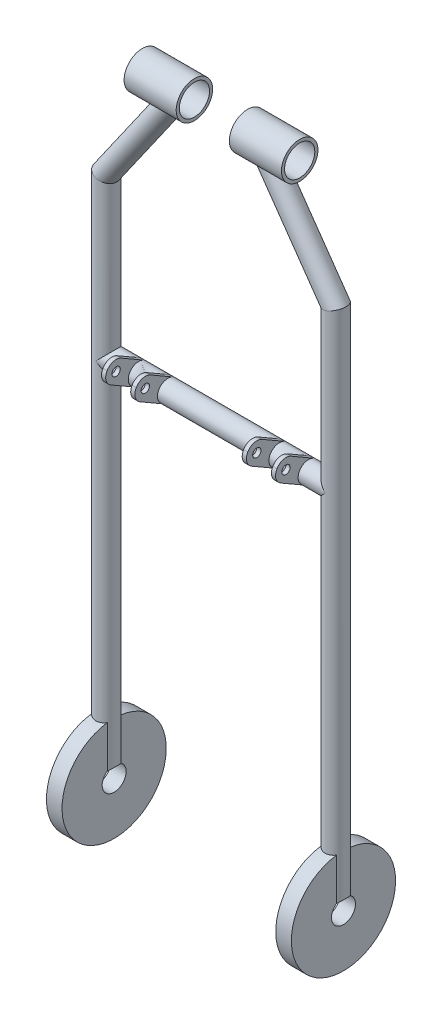
SolidWorks part; units mm, degrees
ref_plane "Alzado" through (0, 0, 0) normal (0, 0, 1) x (1, 0, 0)
ref_plane "Planta" through (0, 0, 0) normal (0, 1, 0) x (1, 0, 0)
ref_plane "Vista lateral" through (0, 0, 0) normal (1, 0, 0) x (0, 0, -1)
sketch "Croquis1" plane through (0, 0, 0) normal (1, 0, 0) x (0, 0, -1)
  circle A0 centre (0, 0) radius 17.5
  circle A1 centre (0, 0) radius 14.5
  dimension "D1" = 35
  dimension "D2" = 3
extrude "Saliente-Extruir1" add sketch "Croquis1" along normal blind 50
sketch "Croquis2" plane through (0, 0, 0) normal (0, 0, 1) x (1, 0, 0)
  line L0 (25, -17.5) -> (-34.5176, -102.5)
  line L1 (-34.5176, -102.5) -> (-34.5176, -602.5)
  line L2 (-34.5176, -102.5) -> (29.5486, -102.5) construction
  line L3 (25, 17.5) -> (25, -17.5) construction
  line L4 (50, 17.5) -> (0, 17.5) construction
  line L5 (0, -17.5) -> (50, -17.5) construction
  line L6 (0, 0) -> (50, 0) construction
  line L7 (50, -17.5) -> (50, 17.5) construction
  dimension "D1" = 85
  dimension "D2" = 500
  dimension "D3" = 55
  dimension "D4" = 64.0663
ref_plane "Plano1" through (25, -17.5, 0) normal (-0.5736, -0.8192, 0) x (0, 0, 1)
sketch "Croquis3" plane through (25, -17.5, 0) normal (-0.5736, -0.8192, 0) x (0, 0, 1)
  circle A0 centre (0, 0) radius 10
  circle A1 centre (0, 0) radius 7
  dimension "D2" = 3
  dimension "D1" = 20
sweep "Barrer1" add profiles "Croquis3" path "Croquis2"
sketch "Croquis4" plane through (50, 0, 0) normal (1, 0, 0) x (0, 0, -1)
  circle A0 centre (0, 0) radius 14.5 construction
  circle A1 centre (0, 0) radius 14.5
extrude "Cortar-Extruir1" cut sketch "Croquis4" against normal through all
sketch "Croquis5" plane through (0.0024, 0.0035, 0) normal (0.5736, 0.8192, 0) x (0.8192, -0.5736, 0)
  arc A4 (40.5164, 0) -> (26.1673, 9.0048) centre (30.5164, 0) ccw
  arc A5 (37.5164, 0) -> (28.2476, 6.6221) centre (30.5164, 0) ccw
  arc A6 (28.2476, -6.6221) -> (37.5164, 0) centre (30.5164, 0) ccw
  arc A7 (26.1673, -9.0048) -> (40.5164, 0) centre (30.5164, 0) ccw
  arc A8 (40.5164, 0) -> (26.1673, 9.0048) centre (30.5164, 0) ccw
  arc A9 (37.5164, 0) -> (28.2476, 6.6221) centre (30.5164, 0) ccw
  arc A10 (28.2476, -6.6221) -> (37.5164, 0) centre (30.5164, 0) ccw
  arc A11 (26.1673, -9.0048) -> (40.5164, 0) centre (30.5164, 0) ccw
  ellipse E2 centre (0.0061, 0) end of major axis (-30.5042, 0) minor radius 17.5 (28.2476, 6.6221) -> (26.1673, 9.0048) ccw
  ellipse E3 centre (0.0061, 0) end of major axis (-30.5042, 0) minor radius 17.5 (26.1673, -9.0048) -> (28.2476, -6.6221) ccw
  ellipse E4 centre (0.0061, 0) end of major axis (-30.5042, 0) minor radius 17.5 (28.2476, 6.6221) -> (26.1673, 9.0048) ccw
  ellipse E5 centre (0.0061, 0) end of major axis (-30.5042, 0) minor radius 17.5 (26.1673, -9.0048) -> (28.2476, -6.6221) ccw
  dimension "D1" = 0
extrude "Saliente-Extruir2" add sketch "Croquis5" along normal up to body separate body
ref_plane "Plano3" through (101, 0, 0) normal (1, 0, 0) x (0, 0, -1)
sketch "Croquis6" plane through (101, 0, 0) normal (1, 0, 0) x (0, 0, -1)
  circle A0 centre (0, 0) radius 14.5 construction
  circle A1 centre (0, 0) radius 17.5 construction
  circle A2 centre (0, 0) radius 14.5
  circle A3 centre (0, 0) radius 17.5
extrude "Saliente-Extruir3" add sketch "Croquis6" along normal blind 50 separate body
sketch "Croquis7" plane through (0, 0, 0) normal (0, 0, 1) x (1, 0, 0)
  line L0 (151, -17.5) -> (151, 17.5) construction
  line L1 (101, -17.5) -> (151, -17.5) construction
  line L2 (101, 17.5) -> (101, -17.5) construction
  line L3 (151, 17.5) -> (101, 17.5) construction
  line L4 (151, -17.5) -> (151, 17.5) construction
  line L5 (101, -17.5) -> (151, -17.5) construction
  line L6 (101, 17.5) -> (101, -17.5) construction
  line L7 (151, 17.5) -> (101, 17.5) construction
  line L8 (126, -17.5) -> (185.5176, -102.5)
  line L9 (185.5176, -102.5) -> (185.5176, -602.5)
  line L10 (185.5176, -102.5) -> (99.3833, -102.5) construction
  dimension "D1" = 85
  dimension "D2" = 500
  dimension "D3" = 86.1343
  dimension "D4" = 55
ref_plane "Plano4" through (126, -17.5, 0) normal (0.5736, -0.8192, 0) x (-0.8192, -0.5736, 0)
sketch "Croquis8" plane through (126, -17.5, 0) normal (0.5736, -0.8192, 0) x (-0.8192, -0.5736, 0)
  circle A0 centre (0, 0) radius 10
  circle A1 centre (0, 0) radius 7
  dimension "D2" = 3
  dimension "D1" = 20
sweep "Barrer2" add profiles "Croquis8" path "Croquis7"
sketch "Croquis9" plane through (49.675, -70.9433, 0) normal (-0.5736, 0.8192, 0) x (0.8192, 0.5736, 0)
  arc A2 (95.4443, 6.6221) -> (95.4443, -6.6221) centre (93.1756, 0) ccw
  arc A3 (97.5246, 9.0048) -> (97.5246, -9.0048) centre (93.1756, 0) ccw
  arc A4 (95.4443, 6.6221) -> (95.4443, -6.6221) centre (93.1756, 0) ccw
  arc A5 (97.5246, 9.0048) -> (97.5246, -9.0048) centre (93.1756, 0) ccw
  ellipse E2 centre (123.6859, 0) end of major axis (93.1756, 0) minor radius 17.5 (97.5246, 9.0048) -> (95.4443, 6.6221) ccw
  ellipse E3 centre (123.6859, 0) end of major axis (93.1756, 0) minor radius 17.5 (95.4443, -6.6221) -> (97.5246, -9.0048) ccw
  ellipse E4 centre (123.6859, 0) end of major axis (93.1756, 0) minor radius 17.5 (97.5246, 9.0048) -> (95.4443, 6.6221) ccw
  ellipse E5 centre (123.6859, 0) end of major axis (93.1756, 0) minor radius 17.5 (95.4443, -6.6221) -> (97.5246, -9.0048) ccw
  dimension "D1" = 0
extrude "Saliente-Extruir4" add sketch "Croquis9" along normal up to surface up to face at (132.5056, -16.5721, 0.0091)
sketch "Croquis10" plane through (0, 0, 0) normal (1, 0, 0) x (0, 0, -1)
  line L0 (10, -102.5) -> (10, -14.3614) construction
  line L1 (-10, -14.3614) -> (-10, -102.5) construction
  line L2 (10, -602.5) -> (10, -102.5) construction
  line L3 (-10, -102.5) -> (-10, -602.5) construction
  line L4 (10, -102.5) -> (10, -14.3614) construction
  line L5 (-10, -14.3614) -> (-10, -102.5) construction
  line L6 (10, -602.5) -> (10, -102.5) construction
  line L7 (-10, -102.5) -> (-10, -602.5) construction
  line L10 (0, -602.5) -> (0, -11.7642) construction
  circle A0 centre (0, -254.3614) radius 10
  dimension "D2" = 20
  dimension "D1" = 240
extrude "Saliente-Extruir5" add sketch "Croquis10" along normal up to surface and the other way up to surface contours A0 up to face at (195.5176, -99.347, 0) other way up to face at (-44.5176, -99.347, 0)
sketch "Croquis11" plane through (0, -602.5, 0) normal (0, -1, 0) x (1, 0, 0)
  line L0 (-34.5176, 0) -> (-44.5176, 0)
  circle A0 centre (-34.5176, 0) radius 10 construction
  circle A1 centre (-34.5176, 0) radius 10 construction
ref_plane "Plano5" through (-34.5176, -602.5, 0) normal (-1, 0, 0) x (0, 0, 1)
sketch "Croquis12" plane through (-34.5176, -602.5, 0) normal (-1, 0, 0) x (0, 0, 1)
  line L0 (-10, 0) -> (10, 0) construction
  circle A0 centre (0, 0) radius 50
  dimension "D1" = 100
extrude "Saliente-Extruir6" add sketch "Croquis12" along normal mid plane 15
chamfer "Chaflán3" distance 7 angle 45 2 edges at (-25.1635, -602.5, -3.5355) (-25.1635, -602.5, 3.5355)
chamfer "Chaflán4" distance 7 angle 45 1 edges at (-44.5176, -602.5, 0)
sketch "Croquis13" plane through (0, -602.5, 0) normal (0, -1, 0) x (1, 0, 0)
  line L0 (185.5176, 0) -> (175.5176, 0) construction
  circle A0 centre (185.5176, 0) radius 10 construction
  circle A1 centre (185.5176, 0) radius 10 construction
ref_plane "Plano6" through (185.5176, -602.5, 0) normal (-1, 0, 0) x (0, 0, 1)
sketch "Croquis14" plane through (185.5176, -602.5, 0) normal (-1, 0, 0) x (0, 0, 1)
  arc A0 (-6.6144, 49.5606) -> (6.6144, 49.5606) centre (0, 0) ccw construction
  arc A1 (-6.6144, 49.5606) -> (6.6144, 49.5606) centre (0, 0) ccw
  circle A2 centre (0, 0) radius 50
extrude "Saliente-Extruir8" add sketch "Croquis14" along normal mid plane 15 contours A2
sketch "Croquis15" plane through (151, 0, 0) normal (1, 0, 0) x (0, 0, -1)
  circle A0 centre (0, 0) radius 14.5 construction
  circle A1 centre (0, 0) radius 14.5
extrude "Cortar-Extruir2" cut sketch "Croquis15" against normal through all contours A1
ref_plane "Plano7" through (75, 0, 0) normal (1, 0, 0) x (0, 0, -1)
sketch "Croquis16" plane through (75, 0, 0) normal (1, 0, 0) x (0, 0, -1)
  line L0 (0, -254.3614) -> (-30.3109, -236.8614)
  line L1 (0, -254.3614) -> (0, -204.3614) construction
  arc A0 (-10, -254.3614) -> (10, -254.3614) centre (0, -254.3614) ccw construction
  arc A1 (10, -254.3614) -> (-10, -254.3614) centre (0, -254.3614) ccw construction
  arc A2 (-10, -254.3614) -> (10, -254.3614) centre (0, -254.3614) ccw
  arc A3 (10, -254.3614) -> (-10, -254.3614) centre (0, -254.3614) ccw
  dimension "D1" = 50
  dimension "D2" = 60
  dimension "D3" = 35
ref_plane "Plano8" through (75, -236.8614, 30.3109) normal (0, 0.5, 0.866) x (1, 0, 0)
sketch "Croquis17" plane through (75, -236.8614, 30.3109) normal (0, 0.5, 0.866) x (1, 0, 0)
  line L0 (120.5176, -301.4969) -> (120.5176, 134.2464) construction
  line L1 (-119.5176, 134.2464) -> (-119.5176, -295.4347) construction
  line L2 (120.5176, -301.4969) -> (120.5176, 134.2464) construction
  line L3 (-119.5176, 134.2464) -> (-119.5176, -295.4347) construction
  line L4 (-100.8574, -10) -> (101.8574, -10) construction
  line L5 (101.8574, 10) -> (-100.8574, 10) construction
  line L6 (-100.8574, -10) -> (101.8574, -10) construction
  line L7 (101.8574, 10) -> (-100.8574, 10) construction
  line L8 (-119.5176, 0) -> (120.5176, 0) construction
  line L9 (-82.5, 10) -> (-78.5, 10)
  line L10 (-82.5, 10) -> (-82.5, -10)
  line L11 (-82.5, -10) -> (-78.5, -10)
  line L12 (-78.5, 10) -> (-78.5, -10)
  line L13 (-82.5, 10) -> (-78.5, -10) construction
  line L14 (-82.5, -10) -> (-78.5, 10) construction
  line L15 (-50.5, 10) -> (-54.5, 10)
  line L16 (-50.5, 10) -> (-50.5, -10)
  line L17 (-50.5, -10) -> (-54.5, -10)
  line L18 (-54.5, 10) -> (-54.5, -10)
  line L19 (-50.5, 10) -> (-54.5, -10) construction
  line L20 (-50.5, -10) -> (-54.5, 10) construction
  line L29 (0, 0) -> (0, 43.3013) construction
  line L30 (0.5, 0) -> (0.5, -10) construction
  line L31 (0, 0) -> (0, 43.3013) construction
  line L32 (52.5, -10) -> (56.5, -10)
  line L33 (52.5, 10) -> (52.5, -10)
  line L34 (52.5, 10) -> (56.5, 10)
  line L35 (56.5, 10) -> (56.5, -10)
  line L36 (84.5, -10) -> (80.5, -10)
  line L37 (80.5, 10) -> (80.5, -10)
  line L38 (84.5, 10) -> (80.5, 10)
  line L39 (84.5, 10) -> (84.5, -10)
  point P12 (-80.5, 0)
  point P17 (-52.5, 0)
  dimension "D1" = 24
  dimension "D2" = 4
  dimension "D3" = 4
  dimension "D4" = 50.5
  dimension "D5" = 52.5
  dimension "D6" = 24
  dimension "D7" = 4
  dimension "D8" = 4
extrude "Saliente-Extruir10" add sketch "Croquis17" against normal up to body separate body contours L12 L11 L10 L9 | L16 L17 L18 L15 | L35 L34 L33 L32 | L36 L37 L38 L39
fillet "Redondeo1" radius 10 8 edges at (157.5, -245.5217, 35.3109) (157.5, -228.2012, 25.3109) (129.5, -245.5217, 35.3109) (129.5, -228.2012, 25.3109) (-5.5, -245.5217, 35.3109) (-5.5, -228.2012, 25.3109) (22.5, -228.2012, 25.3109) (22.5, -245.5217, 35.3109)
sketch "Croquis18" plane through (-7.5, 0, 0) normal (-1, 0, 0) x (0, 0, 1)
  circle A0 centre (21.6506, -241.8614) radius 4
  dimension "D1" = 8
extrude "Cortar-Extruir3" cut sketch "Croquis18" against normal through all
ref_plane "Plano9" through (-52.0176, 0, 0) normal (-1, 0, 0) x (0, 0, 1)
sketch "Croquis19" plane through (-52.0176, 0, 0) normal (-1, 0, 0) x (0, 0, 1)
  line L0 (-10, -602.5) -> (10, -602.5) construction
  circle A0 centre (0, -602.5) radius 50 construction
  arc A1 (-6.6144, -552.9394) -> (6.6144, -552.9394) centre (0, -602.5) ccw construction
  circle A2 centre (0, -602.5) radius 11.5
  dimension "D1" = 23
extrude "Cortar-Extruir4" cut sketch "Croquis19" against normal through all contours A2
equation "\"Diam_Tubo\"=35"
equation "\"D1@Croquis1\"=\"Diam_Tubo\""
equation "\"Grosor_Tubo\"=3"
equation "\"D2@Croquis1\"=\"Grosor_Tubo\""
equation "\"Dist_Sec\"=85"
equation "\"D1@Croquis2\"=\"Dist_Sec\""
equation "\"Diste_sec\" = 500"
equation "\"D2@Croquis2\"=\"Diste_sec\""
equation "\"Inclinacion_Princ\"= 55"
equation "\"D3@Croquis2\"=\"Inclinacion_Princ\""
equation "\"D2@Croquis3\"=\"Grosor_Tubo\""
equation "\"Diam_Tubo2\"=20"
equation "\"D1@Croquis3\"=\"Diam_Tubo2\""
equation "\"Ext_Tubo\"= 50"
equation "\"D1@Saliente-Extruir1\"=\"Ext_Tubo\""
equation "\"D1@Saliente-Extruir3\"=\"Ext_Tubo\""
equation "\"D1@Croquis7\"=\"Dist_Sec\""
equation "\"D2@Croquis7\"=\"Diste_sec\""
equation "\"D4@Croquis7\"=\"Inclinacion_Princ\""
equation "\"D1@Croquis8\"=\"Diam_Tubo2\""
equation "\"D2@Croquis8\"=\"Grosor_Tubo\""
equation "\"Dist_Soporte_Amortiguador\" = 240"
equation "\"D2@Croquis10\"=\"Diam_Tubo2\""
equation "\"Ext_Sop_Rueda\"= 15"
equation "\"D1@Saliente-Extruir6\"=\"Ext_Sop_Rueda\""
equation "\"Tubo_Rueda\"= 100"
equation "\"D1@Saliente-Extruir8\"=\"Ext_Sop_Rueda\""
equation "\"Ang_Perp_SopAmort\" = 60"
equation "\"D2@Croquis16\"=\"Ang_Perp_SopAmort\""
equation "\"Largo_SopAmort\"= 35"
equation "\"D3@Croquis16\"=\"Largo_SopAmort\""
equation "\"Dist_Entre_SopAmort\"= 24"
equation "\"D1@Croquis17\"=\"Dist_Entre_SopAmort\""
equation "\"Grosor_SopAmort\"=4"
equation "\"D2@Croquis17\"=\"Grosor_SopAmort\""
equation "\"D3@Croquis17\"=\"Grosor_SopAmort\""
equation "\"Dist_SopRu_SopAmort\"=36.881"
equation "\"Agujero_Amort\"=8"
equation "\"D1@Croquis10\"=\"Dist_Soporte_Amortiguador\""
equation "\"D1@Croquis12\"=\"Tubo_Rueda\""
equation "\"D1@Croquis18\"=\"Agujero_Amort\""
equation "\"D6@Croquis17\"=\"D1@Croquis17\""
equation "\"D7@Croquis17\"=\"D3@Croquis17\""
equation "\"D8@Croquis17\"=\"D3@Croquis17\""
equation "\"Entrada_Eje\"=23"
equation "\"D1@Croquis19\"=\"Entrada_Eje\""
